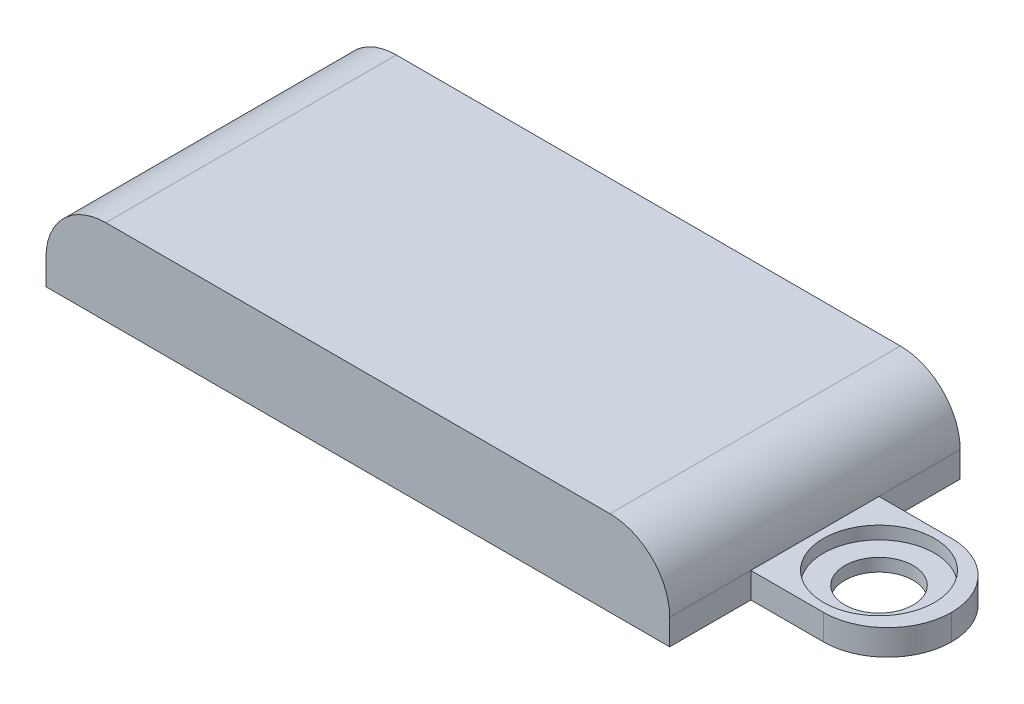
SolidWorks part; units mm, degrees
ref_plane "Front Plane" through (0, 0, 0) normal (0, 0, 1) x (1, 0, 0)
ref_plane "Top Plane" through (0, 0, 0) normal (0, 1, 0) x (1, 0, 0)
ref_plane "Right Plane" through (0, 0, 0) normal (1, 0, 0) x (0, 0, -1)
sketch "Sketch1" plane through (0, 0, 0) normal (0, 1, 0) x (1, 0, 0)
  line L1 (-32.986, 15.3595) -> (40.014, 15.3595)
  line L2 (-32.986, 15.3595) -> (-32.986, -18.6405)
  line L3 (-32.986, -18.6405) -> (40.014, -18.6405)
  line L4 (40.014, 15.3595) -> (40.014, -18.6405)
  dimension "D1" = 73
  dimension "D2" = 34
extrude "base" add sketch "Sketch1" along normal blind 10
sketch "Sketch3" plane through (0, 0, 0) normal (0, -1, 0) x (1, 0, 0)
  line L0 (-32.986, -15.3595) -> (-32.986, 18.6405) construction
  line L1 (-31.486, 17.1405) -> (38.514, 17.1405)
  line L2 (-31.486, 17.1405) -> (-31.486, -13.8595)
  line L3 (-31.486, -13.8595) -> (38.514, -13.8595)
  line L4 (38.514, 17.1405) -> (38.514, -13.8595)
  line L5 (-32.986, 18.6405) -> (40.014, 18.6405) construction
  line L6 (40.014, -15.3595) -> (-32.986, -15.3595) construction
  line L7 (40.014, 18.6405) -> (40.014, -15.3595) construction
  dimension "D1" = 1.5
  dimension "D2" = 1.5
  dimension "D3" = 1.5
  dimension "D4" = 1.5
extrude "inside cut" cut sketch "Sketch3" against normal blind 8.5
fillet "inside fillet" radius 5.5 2 edges at (38.514, 8.5, 1.6405) (-31.486, 8.5, 1.6405)
fillet "outside fillet" radius 7 2 edges at (40.014, 10, 1.6405) (-32.986, 10, 1.6405)
sketch "Sketch4" plane through (0, 0, 0) normal (0, -1, 0) x (1, 0, 0)
  line L0 (40.014, 18.6405) -> (40.014, -15.3595) construction
  line L1 (40.014, 9.1405) -> (56.014, 9.1405)
  line L2 (40.014, 9.1405) -> (40.014, -5.8595)
  line L3 (40.014, -5.8595) -> (56.014, -5.8595)
  line L4 (56.014, 9.1405) -> (56.014, -5.8595)
  line L5 (40.014, -15.3595) -> (-32.986, -15.3595) construction
  dimension "D1" = 15
  dimension "D2" = 16
  dimension "D3" = 9.5
extrude "screw square" add sketch "Sketch4" against normal blind 3
fillet "screw fillet" radius 7.5 2 edges at (56.014, 1.5, -5.8595) (56.014, 1.5, 9.1405)
sketch "Sketch5" plane through (0, 3, 0) normal (0, 1, 0) x (1, 0, 0)
  line L0 (48.514, -9.1405) -> (40.014, -9.1405) construction
  line L1 (40.014, -9.1405) -> (40.014, 5.8595) construction
  circle A0 centre (47.514, -1.6405) radius 4
  dimension "D1" = 8
  dimension "D2" = 7.5
  dimension "D3" = 7.5
extrude "Cut-Extrude3" cut sketch "Sketch5" against normal blind 3
sketch "Sketch7" plane through (0, 3, 0) normal (0, 1, 0) x (1, 0, 0)
  circle A0 centre (47.514, -1.6405) radius 6.5
  dimension "D1" = 13
extrude "Cut-Extrude4" cut sketch "Sketch7" against normal blind 1.5
